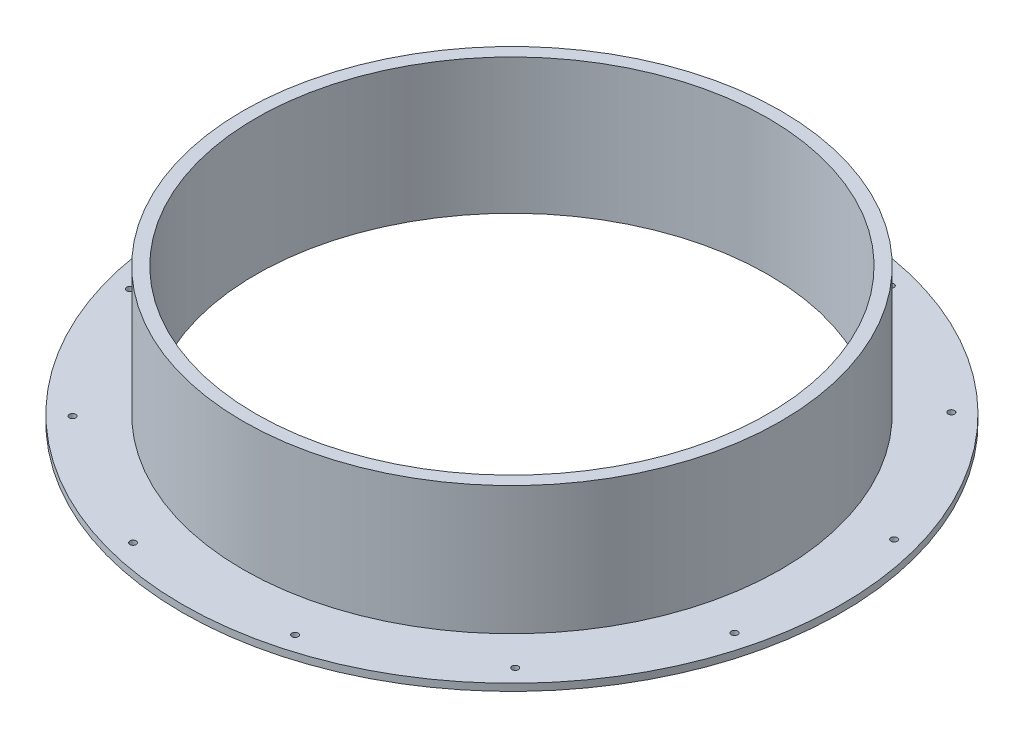
SolidWorks part; units mm, degrees
note: '?' marks a value the reader was unsure of.
ref_plane "Front Plane" through (0, 0, 0) normal (0, 0, 1) x (1, 0, 0)
ref_plane "Top Plane" through (0, 0, 0) normal (0, 1, 0) x (1, 0, 0)
ref_plane "Right Plane" through (0, 0, 0) normal (1, 0, 0) x (0, 0, -1)
sketch "Sketch2" plane through (0, 0, 0) normal (0, 1, 0) x (1, 0, 0)
  circle A0 centre (0, 0) radius 49.03
  dimension "D1" = 98.06
sketch "Sketch3" plane through (0, 0, 0) normal (0, 1, 0) x (1, 0, 0)
  circle A0 centre (0, 0) radius 40.005
  dimension "D1" = 80.01
extrude "Boss-Extrude1" add sketch "Sketch3" along normal blind 20.14 contours A0
sketch "Sketch4" plane through (0, 20.14, 0) normal (0, 1, 0) x (1, 0, 0)
  circle A0 centre (0, 0) radius 38.1
  dimension "D1" = 76.2
extrude "Cut-Extrude1" cut sketch "Sketch4" against normal blind 20.14
extrude "Boss-Extrude2" add sketch "Sketch2" along normal blind 1.05
sketch "Sketch6" plane through (0, 1.05, 0) normal (0, 1, 0) x (1, 0, 0)
  circle A0 centre (0, 0) radius 38.1
  dimension "D1" = 76.2
extrude "Cut-Extrude2" cut sketch "Sketch6" against normal blind 1.05
ref_axis "Axis2" through (0, 21.147, 0) along (0, -1, 0)?
sketch "Sketch7" plane through (0, 0, 0) normal (0, 1, 0) x (1, 0, 0)
  circle A0 centre (0, 0) radius 40.5
  dimension "D1" = 81
sketch "Sketch10" plane through (0, 0, 0) normal (0, 1, 0) x (1, 0, 0)
  line L0 (-44.5596, -12.2989) -> (-32.4403, -32.9309)
  line L1 (44.5596, 12.2989) -> (32.4403, 32.9309)
  line L2 (32.4403, 32.9309) -> (11.6287, 44.7392)
  line L3 (11.6287, 44.7392) -> (-12.2989, 44.5596)
  line L4 (-12.2989, 44.5596) -> (-32.9309, 32.4403)
  line L5 (-32.9309, 32.4403) -> (-44.7392, 11.6287)
  line L6 (-44.7392, 11.6287) -> (-44.5596, -12.2989)
  line L7 (-32.4403, -32.9309) -> (-11.6287, -44.7392)
  line L8 (-11.6287, -44.7392) -> (12.2989, -44.5596)
  line L9 (12.2989, -44.5596) -> (32.9309, -32.4403)
  line L10 (32.9309, -32.4403) -> (44.7392, -11.6287)
  line L11 (44.7392, -11.6287) -> (44.5596, 12.2989)
  circle A0 centre (0, 0) radius 44.6506 construction
  dimension "D1" = 89.3013
hole_wizard "M1.2x0.25 Tapped Hole2" positions "3DSketch3" profile "Sketch12" tap size "M1.2x0.25" standard "ANSI Metric" end condition through all
sketch3d "3DSketch3"
  point P0 (-12.2989, 1.05, -44.5596)
  point P2 (11.6287, 1.05, -44.7392)
  point P4 (32.4403, 1.05, -32.9309)
  point P6 (44.5596, 1.05, -12.2989)
  point P8 (44.7392, 1.05, 11.6287)
  point P10 (32.9309, 1.05, 32.4403)
  point P12 (12.2989, 1.05, 44.5596)
  point P14 (-11.6287, 1.05, 44.7392)
  point P16 (-32.4403, 1.05, 32.9309)
  point P18 (-44.5596, 1.05, 12.2989)
  point P20 (-44.7392, 1.05, -11.6287)
  point P22 (-32.9309, 1.05, -32.4403)
sketch "Sketch12" plane through (-12.2989, 1.05, -44.5596) normal (1, 0, 0) x (0, 0, 1)
  line L0 (0, 0) -> (0, 1.05)
  line L1 (0, 1.05) -> (0.475, 1.05)
  line L2 (0.475, 1.05) -> (0.475, 0)
  line L5 (0.475, 0) -> (0, 0)
  line L11 (0, -6.35) -> (0, 107.95) construction
  dimension "Thru Tap Drill Dia." = 0.95
  dimension "Thru Tap Drill Depth" = 1.05
cosmetic thread "Hole Thread14" parameters "D2"=1.2
cosmetic thread "Hole Thread15" parameters "D2"=1.2
cosmetic thread "Hole Thread16" parameters "D2"=1.2
cosmetic thread "Hole Thread17" parameters "D2"=1.2
cosmetic thread "Hole Thread18" parameters "D2"=1.2
cosmetic thread "Hole Thread19" parameters "D2"=1.2
cosmetic thread "Hole Thread20" parameters "D2"=1.2
cosmetic thread "Hole Thread21" parameters "D2"=1.2
cosmetic thread "Hole Thread22" parameters "D2"=1.2
cosmetic thread "Hole Thread23" parameters "D2"=1.2
cosmetic thread "Hole Thread24" parameters "D2"=1.2
cosmetic thread "Hole Thread25" parameters "D2"=1.2
hole_wizard "M1.2x0.25 Tapped Hole3" [suppressed] positions "Sketch13" profile "Sketch14"
sketch "Sketch13" plane through (62.0752, 0, -23.9492) normal (0, 1, 0) x (1, 0, 0)
  point P0 (-95.0061, 8.4911)
  point P3 (-74.3741, 20.6104)
  point P6 (-50.4466, 20.79)
  point P9 (-29.6349, 8.9817)
  point P12 (-17.5156, -11.6503)
  point P15 (-17.3361, -35.5778)
  point P18 (-29.1443, -56.3895)
  point P21 (-49.7764, -68.5087)
  point P24 (-73.7039, -68.6883)
  point P27 (-94.5155, -56.8801)
  point P30 (-106.6348, -36.248)
  point P33 (-106.8144, -12.3205)
sketch "Sketch14" plane through (0, 0, 0) normal (0, 0, 1) x (1, 0, 0)
  line L0 (0, 0) -> (0, 9.45)
  line L1 (0, 9.45) -> (0.475, 9.45)
  line L2 (0.475, 9.45) -> (0.475, 0)
  line L3 (0.475, 0) -> (0, 0)
  line L4 (0, -6.35) -> (0, 107.95) construction
  dimension "Thru Tap Drill Dia." = 0.95
  dimension "Thru Tap Drill Depth" = 9.45
equation "\"ODia\"= 3.15in"
equation "\"IDia\"= 3in"
equation "\"PlateDia\"= 98.06mm"
equation "\"PlateThick\"= 1.05mm"
equation "\"Motorh\"= 20.14mm"
equation "\"IDiaw\"= 4.7mm"
equation "\"IIDia\"= 3in"
equation "\"HoleDIa\"= 89.301253mm"
